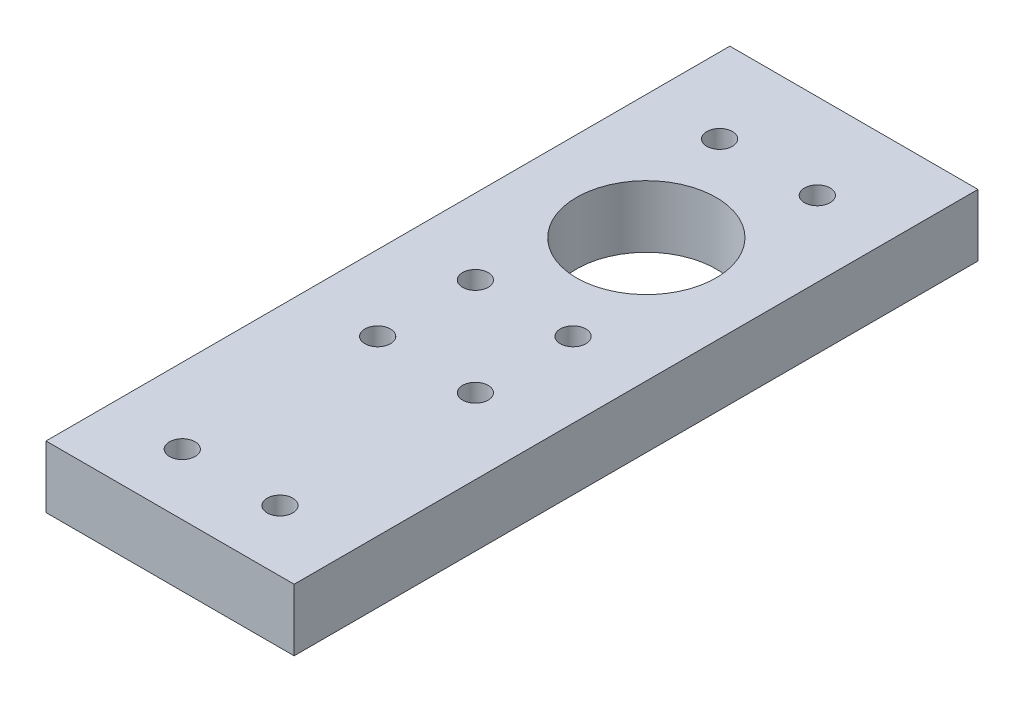
SolidWorks part; units mm, degrees
ref_plane "Front Plane" through (0, 0, 0) normal (0, 0, 1) x (1, 0, 0)
ref_plane "Top Plane" through (0, 0, 0) normal (0, 1, 0) x (1, 0, 0)
ref_plane "Right Plane" through (0, 0, 0) normal (1, 0, 0) x (0, 0, -1)
sketch "Sketch2" plane through (0, 0, 0) normal (0, 1, 0) x (1, 0, 0)
  line L1 (0, 0) -> (101.6, 0)
  line L2 (0, 0) -> (0, 280)
  line L3 (0, 280) -> (101.6, 280)
  line L4 (101.6, 0) -> (101.6, 280)
  dimension "D1" = 101.6
  dimension "D2" = 280
extrude "Boss-Extrude1" add sketch "Sketch2" along normal blind 25.4
sketch "Sketch3" plane through (0, 25.4, 0) normal (0, 1, 0) x (1, 0, 0)
  line L1 (0, 280) -> (50.8, 280)
  line L2 (0, 280) -> (0, 195)
  line L3 (0, 195) -> (50.8, 195)
  line L4 (50.8, 280) -> (50.8, 195)
  line L5 (30.8, 245) -> (70.8, 245)
  line L6 (30.8, 245) -> (30.8, 145)
  line L7 (30.8, 145) -> (70.8, 145)
  line L8 (70.8, 245) -> (70.8, 145)
  line L9 (30.8, 245) -> (70.8, 145) construction
  line L10 (30.8, 145) -> (70.8, 245) construction
  circle A0 centre (70.8, 245) radius 5.25
  circle A1 centre (30.8, 245) radius 5.25
  circle A2 centre (70.8, 145) radius 5.25
  circle A3 centre (30.8, 145) radius 5.25
  circle A4 centre (50.8, 195) radius 28.575
  dimension "D1" = 50.8
  dimension "D2" = 85
  dimension "D3" = 40
  dimension "D4" = 100
extrude "Cut-Extrude1" cut sketch "Sketch3" against normal blind 25.4 contours A1 | A0 | A4 | A2 | A3
sketch "Sketch4" plane through (0, 25.4, 0) normal (0, 1, 0) x (1, 0, 0)
  line L1 (0, 280) -> (50.8, 280)
  line L2 (0, 280) -> (0, 65)
  line L3 (0, 65) -> (50.8, 65)
  line L4 (50.8, 280) -> (50.8, 65)
  line L5 (30.8, 25) -> (70.8, 25)
  line L6 (30.8, 25) -> (30.8, 105)
  line L7 (30.8, 105) -> (70.8, 105)
  line L8 (70.8, 25) -> (70.8, 105)
  line L9 (30.8, 25) -> (70.8, 105) construction
  line L10 (30.8, 105) -> (70.8, 25) construction
  circle A0 centre (70.8, 105) radius 5.25
  circle A1 centre (30.8, 105) radius 5.25
  circle A2 centre (30.8, 25) radius 5.25
  circle A3 centre (70.8, 25) radius 5.25
  dimension "D1" = 50.8
  dimension "D2" = 215
  dimension "D3" = 40
  dimension "D4" = 80
extrude "Cut-Extrude2" cut sketch "Sketch4" against normal blind 25.4 contours A1 | A0 | A3 | A2
